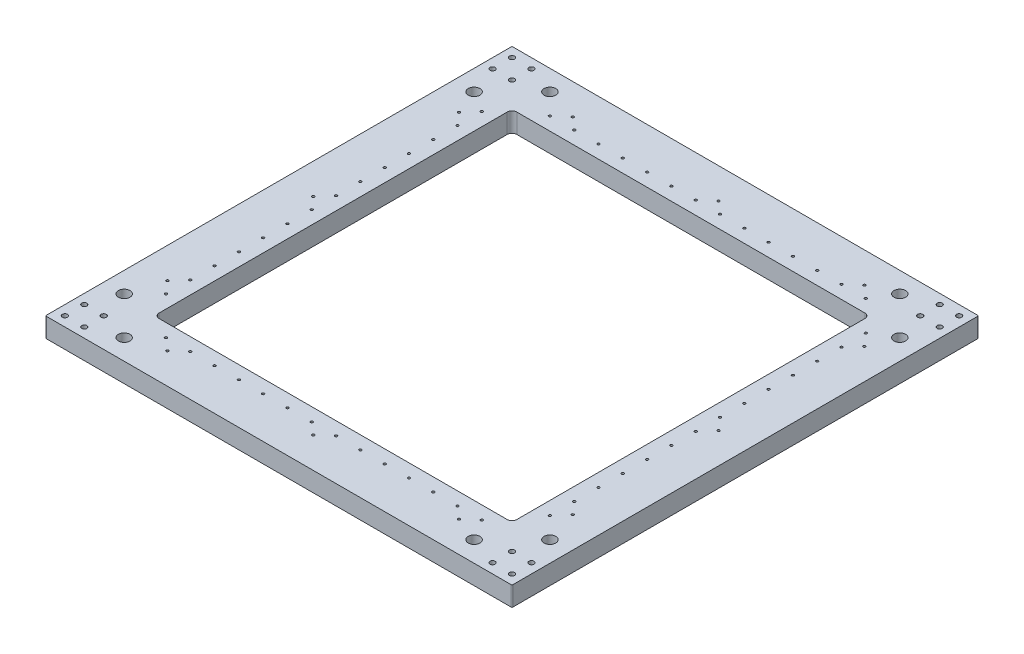
SolidWorks part; units mm, degrees
material "ASTM A36 Steel"
ref_plane "Front Plane" through (0, 0, 0) normal (0, 0, 1) x (1, 0, 0)
ref_plane "Top Plane" through (0, 0, 0) normal (0, 1, 0) x (1, 0, 0)
ref_plane "Right Plane" through (0, 0, 0) normal (1, 0, 0) x (0, 0, -1)
sketch "Sketch1" plane through (0, 0, 0) normal (0, 1, 0) x (1, 0, 0)
  line L1 (240, -240) -> (-240, -240)
  line L2 (240, -240) -> (240, 240)
  line L3 (240, 240) -> (-240, 240)
  line L4 (-240, -240) -> (-240, 240)
  line L5 (240, -240) -> (-240, 240) construction
  line L6 (240, 240) -> (-240, -240) construction
  point P0 (0, 0)
  dimension "D1" = 480
  dimension "D2" = 480
extrude "Boss-Extrude1" add sketch "Sketch1" along normal blind 20
sketch "Sketch2" plane through (0, 20, 0) normal (0, 1, 0) x (1, 0, 0)
  line L0 (240, 240) -> (-240, 240) construction
  line L10 (-240, 240) -> (-240, -240) construction
  line L15 (-240, 159) -> (-198, 159)
  line L16 (-240, 159) -> (-240, 201)
  line L17 (-164.5, 203.5) -> (-195.5, 203.5)
  line L27 (-240, 201) -> (-198, 201)
  line L33 (-198, 159) -> (-198, 201)
  line L35 (-240, 159) -> (-198, 201) construction
  line L36 (-240, 201) -> (-198, 159) construction
  line L37 (-159, 198) -> (-201, 198)
  line L38 (-159, 198) -> (-159, 240)
  line L39 (-159, 240) -> (-201, 240)
  line L40 (-201, 198) -> (-201, 240)
  line L41 (-159, 198) -> (-201, 240) construction
  line L42 (-159, 240) -> (-201, 198) construction
  line L43 (-198, 196) -> (-203, 201)
  line L44 (-164.5, 203.5) -> (-164.5, 234.5)
  line L45 (-164.5, 234.5) -> (-195.5, 234.5)
  line L46 (-195.5, 203.5) -> (-195.5, 234.5)
  line L47 (-164.5, 203.5) -> (-195.5, 234.5) construction
  line L48 (-164.5, 234.5) -> (-195.5, 203.5) construction
  line L49 (-203.5, 164.5) -> (-234.5, 164.5)
  line L50 (-203.5, 164.5) -> (-203.5, 195.5)
  line L51 (-203.5, 195.5) -> (-234.5, 195.5)
  line L52 (-234.5, 164.5) -> (-234.5, 195.5)
  line L53 (-203.5, 164.5) -> (-234.5, 195.5) construction
  line L54 (-203.5, 195.5) -> (-234.5, 164.5) construction
  line L55 (-196, 198) -> (-201, 203)
  line L56 (-203, 201) -> (-201, 203) construction
  point P1 (-219, 180)
  point P5 (-180, 219)
  point P23 (-219, 180)
  point P27 (-180, 219)
  dimension "D1" = 5
  dimension "D2" = 45
  dimension "D3" = 42
  dimension "D4" = 31
  dimension "D5" = 45
  dimension "D6" = 5
  dimension "D7" = 60
hole_wizard "M5 Clearance Hole1" positions "Sketch6" profile "Sketch7" hole size "M5" standard "ANSI Metric" end condition through all
sketch "Sketch6" plane through (0, 20, 0) normal (0, 1, 0) x (1, 0, 0)
  line L1 (-210, 210) -> (-230, 210) construction
  line L2 (-210, 210) -> (-210, 230) construction
  line L3 (-210, 230) -> (-230, 230) construction
  line L4 (-230, 210) -> (-230, 230) construction
  line L5 (-210, 210) -> (-230, 230) construction
  line L6 (-210, 230) -> (-230, 210) construction
  line L7 (240, 240) -> (-240, 240) construction
  line L8 (-240, 240) -> (-240, -240) construction
  point P2 (-230, 230)
  point P109 (-210, 210)
  point P110 (-210, 230)
  point P111 (-230, 210)
  dimension "D1" = 20
  dimension "D2" = 10
  dimension "D3" = 10
sketch "Sketch7" plane through (-230, 20, -230) normal (1, 0, 0) x (0, 0, 1)
  line L0 (0, 0) -> (0, 20)
  line L1 (0, 20) -> (2.65, 20)
  line L2 (2.65, 20) -> (2.65, 0)
  line L5 (2.65, 0) -> (0, 0)
  line L11 (0, -6.35) -> (0, 107.95) construction
  dimension "Thru Hole Dia." = 5.3
  dimension "Thru Hole Depth" = 20
hole_wizard "Bearing Press Fit" positions "Sketch8" profile "Sketch9" hole size "Ø12.0" standard "ANSI Metric" end condition through all
sketch "Sketch8" plane through (0, 20, 0) normal (0, 1, 0) x (1, 0, 0)
  line L1 (-159, 240) -> (-201, 198) construction
  point P8 (-180, 219)
  point P12 (-219, 180)
sketch "Sketch9" plane through (-180, 20, -219) normal (1, 0, 0) x (0, 0, 1)
  line L0 (0, 0) -> (0, 20)
  line L1 (0, 20) -> (6, 20)
  line L2 (6, 20) -> (6, 0)
  line L5 (6, 0) -> (0, 0)
  line L11 (0, -6.35) -> (0, 107.95) construction
  dimension "Thru Hole Dia." = 12
  dimension "Thru Hole Depth" = 20
ref_axis "Axis1" through (0, 8.4, 0) along (0, -1, 0)
pattern_circular "CirPattern1" count 4 over 360 about axis through (0, 8.4, 0) along (0, -1, 0) of "M5 Clearance Hole1", "Bearing Press Fit"
sketch "Sketch5" plane through (0, 20, 0) normal (0, 1, 0) x (1, 0, 0)
  line L1 (184, -184) -> (-184, -184)
  line L2 (184, -184) -> (184, 184)
  line L3 (184, 184) -> (-184, 184)
  line L4 (-184, -184) -> (-184, 184)
  line L5 (184, -184) -> (-184, 184) construction
  line L6 (184, 184) -> (-184, -184) construction
  point P0 (0, 0)
  dimension "D1" = 368
extrude "Cut-Extrude1" cut sketch "Sketch5" against normal up to surface (20 mm away) up to face at (-219, 0, 186)
sketch "Sketch10" plane through (0, 0, 0) normal (0, 1, 0) x (1, 0, 0)
  line L5 (184, 184) -> (-184, 184) construction
  line L6 (204, -204) -> (-204, -204)
  line L14 (204, -204) -> (204, 204)
  line L15 (204, 204) -> (-204, 204)
  line L16 (-204, -204) -> (-204, 204)
  line L17 (204, -204) -> (-204, 204) construction
  line L18 (204, 204) -> (-204, -204) construction
  line L19 (191.5, -191.5) -> (-191.5, -191.5)
  line L20 (191.5, -191.5) -> (191.5, 191.5)
  line L21 (191.5, 191.5) -> (-191.5, 191.5)
  line L22 (-191.5, -191.5) -> (-191.5, 191.5)
  line L23 (191.5, -191.5) -> (-191.5, 191.5) construction
  line L24 (191.5, 191.5) -> (-191.5, -191.5) construction
  point P0 (0, 0)
  point P6 (0, 0)
  dimension "D2" = 7.5
  dimension "D1" = 12.5
extrude "Linear Rail Slot" cut sketch "Sketch10" along normal blind 2.5
fillet "Fillet2" radius 5 4 edges at (-184, 10, 184) (184, 10, 184) (184, 10, -184) (-184, 10, -184)
fillet "Fillet1" radius 1 4 edges at (240, 10, -240) (-240, 10, -240) (240, 10, 240) (-240, 10, 240)
sketch "Sketch11" plane through (0, 2.5, 0) normal (0, -1, 0) x (1, 0, 0)
  line L0 (-176, 197.5) -> (184, 197.5)
  line L1 (-191.5, 191.5) -> (191.5, 191.5) construction
  line L2 (204, 204) -> (204, -204) construction
  point P2 (0, 0)
  point P16 (166.5, 197.5)
  point P18 (141.5, 197.5)
  point P19 (116.5, 197.5)
  point P20 (91.5, 197.5)
  point P21 (66.5, 197.5)
  point P22 (41.5, 197.5)
  point P23 (16.5, 197.5)
  point P24 (-8.5, 197.5)
  point P25 (-33.5, 197.5)
  point P26 (-58.5, 197.5)
  point P28 (-83.5, 197.5)
  point P29 (-108.5, 197.5)
  point P30 (-133.5, 197.5)
  point P31 (-158.5, 197.5)
  dimension "D1" = 360
  dimension "D2" = 6
  dimension "D4" = 14
  dimension "D5" = 25
  dimension "D6" = 20
  dimension "D3" = 17.5
hole_wizard "Tap Drill for M3x0.5 Tap1" positions "Sketch12" profile "Sketch13" hole size "M3x0.5" standard "ANSI Metric" end condition through all
sketch "Sketch12" plane through (0, 2.5, 0) normal (0, -1, 0) x (-1, 0, 0)
  line L0 (176, -197.5) -> (-184, -197.5) construction
  point P28 (-166.5, -197.5)
  point P31 (-141.5, -197.5)
  point P34 (-116.5, -197.5)
  point P37 (-91.5, -197.5)
  point P40 (-66.5, -197.5)
  point P43 (-41.5, -197.5)
  point P46 (-16.5, -197.5)
  point P49 (8.5, -197.5)
  point P51 (33.5, -197.5)
  point P54 (58.5, -197.5)
  point P57 (83.5, -197.5)
  point P61 (108.5, -197.5)
  point P64 (133.5, -197.5)
  point P67 (158.5, -197.5)
  point P71 (8.5, -197.5)
  point P73 (78.4398, -197.5)
sketch "Sketch13" plane through (166.5, 2.5, 197.5) normal (1, 0, 0) x (0, 0, -1)
  line L0 (0, 0) -> (0, 17.5)
  line L1 (0, 17.5) -> (1.25, 17.5)
  line L2 (1.25, 17.5) -> (1.25, 0)
  line L5 (1.25, 0) -> (0, 0)
  line L11 (0, -6.35) -> (0, 107.95) construction
  dimension "Thru Hole Dia." = 2.5
  dimension "Thru Hole Depth" = 17.5
sketch "Sketch14" plane through (0, 0, 0) normal (0, -1, 0) x (1, 0, 0)
  line L1 (-133.5, 203.5) -> (-158.5, 203.5)
  line L2 (-130.5, 206.5) -> (-130.5, 210.5)
  line L3 (-133.5, 213.5) -> (-158.5, 213.5)
  line L4 (-161.5, 206.5) -> (-161.5, 210.5)
  line L5 (-130.5, 203.5) -> (-161.5, 213.5) construction
  line L6 (-130.5, 213.5) -> (-161.5, 203.5) construction
  line L7 (-191.5, 191.5) -> (191.5, 191.5) construction
  line L8 (-158.5, 197.5) -> (-133.5, 197.5) construction
  line L19 (16.5, 203.5) -> (-8.5, 203.5)
  line L25 (19.5, 206.5) -> (19.5, 210.5)
  line L26 (16.5, 213.5) -> (-8.5, 213.5)
  line L31 (-11.5, 206.5) -> (-11.5, 210.5)
  line L32 (19.5, 203.5) -> (-11.5, 213.5) construction
  line L33 (19.5, 213.5) -> (-11.5, 203.5) construction
  line L34 (-8.5, 197.5) -> (16.5, 197.5) construction
  line L35 (166.5, 203.5) -> (141.5, 203.5)
  line L36 (169.5, 206.5) -> (169.5, 210.5)
  line L37 (166.5, 213.5) -> (141.5, 213.5)
  line L38 (138.5, 206.5) -> (138.5, 210.5)
  line L39 (169.5, 203.5) -> (138.5, 213.5) construction
  line L40 (169.5, 213.5) -> (138.5, 203.5) construction
  line L41 (141.5, 197.5) -> (166.5, 197.5) construction
  arc A3 (-130.5, 210.5) -> (-133.5, 213.5) centre (-133.5, 210.5) ccw
  arc A4 (-133.5, 203.5) -> (-130.5, 206.5) centre (-133.5, 206.5) ccw
  arc A5 (-158.5, 203.5) -> (-161.5, 206.5) centre (-158.5, 206.5) cw
  arc A6 (-158.5, 213.5) -> (-161.5, 210.5) centre (-158.5, 210.5) ccw
  arc A7 (19.5, 210.5) -> (16.5, 213.5) centre (16.5, 210.5) ccw
  arc A8 (16.5, 203.5) -> (19.5, 206.5) centre (16.5, 206.5) ccw
  arc A9 (-8.5, 203.5) -> (-11.5, 206.5) centre (-8.5, 206.5) cw
  arc A10 (-8.5, 213.5) -> (-11.5, 210.5) centre (-8.5, 210.5) ccw
  arc A11 (169.5, 210.5) -> (166.5, 213.5) centre (166.5, 210.5) ccw
  arc A12 (166.5, 203.5) -> (169.5, 206.5) centre (166.5, 206.5) ccw
  arc A13 (141.5, 203.5) -> (138.5, 206.5) centre (141.5, 206.5) cw
  arc A14 (141.5, 213.5) -> (138.5, 210.5) centre (141.5, 210.5) ccw
  point P0 (-146, 208.5)
  point P12 (-146, 197.5)
  point P24 (0, 0)
  point P25 (-158.5, 197.5)
  point P26 (4, 208.5)
  point P45 (154, 208.5)
  dimension "D5" = 3
  dimension "D4" = 3
  dimension "D1" = 31
  dimension "D2" = 12
  dimension "D3" = 10
  dimension "D7" = 25
  dimension "D6" = 150
extrude "Cut-Extrude2" cut sketch "Sketch14" against normal offset from surface (3.5 mm away) 1 up to face at (166.5, 2.5, 196.25) offset beyond the face yes
hole_wizard "Tap Drill for M3x0.5 Tap2" positions "Sketch17" profile "Sketch18" hole size "M3x0.5" standard "ANSI Metric" end condition through all
sketch "Sketch17" plane through (0, 3.5, 0) normal (0, -1, 0) x (-1, 0, 0)
  point P0 (-154, -208.5)
  point P3 (-4, -208.5)
  point P6 (146, -208.5)
sketch "Sketch18" plane through (154, 3.5, 208.5) normal (1, 0, 0) x (0, 0, -1)
  line L0 (0, 0) -> (0, 16.5)
  line L1 (0, 16.5) -> (1.25, 16.5)
  line L2 (1.25, 16.5) -> (1.25, 0)
  line L5 (1.25, 0) -> (0, 0)
  line L11 (0, -6.35) -> (0, 107.95) construction
  dimension "Thru Hole Dia." = 2.5
  dimension "Thru Hole Depth" = 16.5
fillet "Fillet3" radius 3 6 edges at (168.1583, 1.25, 204) (139.8417, 1.25, 204) (18.1583, 1.25, 204) (-10.1583, 1.25, 204) (-160.1583, 1.25, 204) (-131.8417, 1.25, 204)
ref_plane "Plane1" through (0, 0, 0) normal (0.7071, 0, 0.7071) x (0.7071, 0, -0.7071)
mirror "Mirror3" about plane through (0, 0, 0) normal (0.7071, 0, 0.7071) of "Tap Drill for M3x0.5 Tap2", "Cut-Extrude2", "Tap Drill for M3x0.5 Tap1"
mirror "Mirror5" about plane through (0, 0, 0) normal (0, 0, 1) of "Tap Drill for M3x0.5 Tap2", "Cut-Extrude2", "Tap Drill for M3x0.5 Tap1"
mirror "Mirror7" about plane through (0, 0, 0) normal (0.7071, 0, 0.7071) of "Mirror5"
